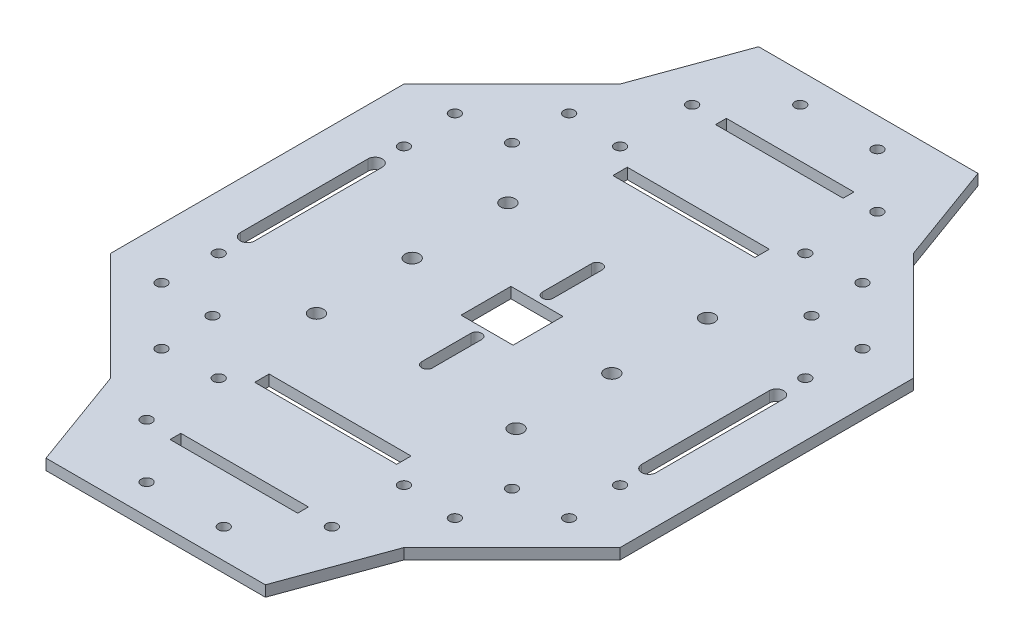
SolidWorks part; units mm, degrees
ref_plane "前视基准面" through (0, 0, 0) normal (0, 0, 1) x (1, 0, 0)
ref_plane "上视基准面" through (0, 0, 0) normal (0, 1, 0) x (1, 0, 0)
ref_plane "右视基准面" through (0, 0, 0) normal (1, 0, 0) x (0, 0, -1)
other "Configuration Table"
sketch "草图1" plane through (0, 0, 0) normal (0, 1, 0) x (1, 0, 0)
  line L0 (-70.7107, -70.7107) -> (70.7107, -70.7107)
  line L3 (70.7107, -70.7107) -> (70.7107, 70.7107)
  line L4 (70.7107, 70.7107) -> (-70.7107, 70.7107)
  line L5 (-70.7107, 70.7107) -> (-70.7107, -70.7107)
extrude "凸台-拉伸1" add sketch "草图1" along normal blind 3
sketch "草图2" plane through (0, 0, 0) normal (0, 1, 0) x (1, 0, 0)
  line L0 (-70.7107, 70.7107) -> (-40.7107, 70.7107)
  line L1 (70.7107, 70.7107) -> (-70.7107, 70.7107) construction
  line L2 (-70.7107, 70.7107) -> (-70.7107, 40.7107)
  line L3 (-70.7107, 70.7107) -> (-70.7107, -70.7107) construction
  line L4 (-40.7107, 70.7107) -> (-70.7107, 40.7107)
extrude "切除-拉伸1" cut sketch "草图2" along normal blind 3
mirror "镜向1" about plane through (0, 0, 0) normal (1, 0, 0) of "切除-拉伸1" second plane through (0, 0, 0) second plane normal (0, 0, 1)
sketch "草图3" plane through (0, 0, 0) normal (0, 1, 0) x (1, 0, 0)
  circle A0 centre (-56.5685, 40.7107) radius 1.5
  circle A1 centre (-40.7107, 56.5685) radius 1.5
  circle A2 centre (-41.5685, 41.5685) radius 1.5
extrude "切除-拉伸2" cut sketch "草图3" along normal blind 3
mirror "镜向2" about plane through (0, 0, 0) normal (0, 0, 1) of "切除-拉伸2" second plane through (0, 0, 0) second plane normal (1, 0, 0)
sketch "草图4" plane through (0, 0, 0) normal (0, 1, 0) x (1, 0, 0)
  circle A0 centre (-27.7107, 26.5685) radius 2
  circle A1 centre (-27.7107, -26.5685) radius 2
  circle A2 centre (-27.7107, 0) radius 2
extrude "切除-拉伸3" cut sketch "草图4" along normal blind 3
mirror "镜向3" about plane through (0, 0, 0) normal (1, 0, 0) of "切除-拉伸3"
sketch "草图5" plane through (0, 0, 0) normal (0, 1, 0) x (1, 0, 0)
  circle A0 centre (-55.7107, 25.7107) radius 1.5
extrude "切除-拉伸4" cut sketch "草图5" along normal blind 3
mirror "镜向4" about plane through (0, 0, 0) normal (1, 0, 0) of "切除-拉伸4" second plane through (0, 0, 0) second plane normal (0, 0, 1)
sketch "草图6" plane through (0, 0, 0) normal (0, 1, 0) x (1, 0, 0)
  circle A0 centre (-25.7107, 55.7107) radius 1.5
extrude "切除-拉伸5" cut sketch "草图6" along normal blind 3
mirror "镜向5" about plane through (0, 0, 0) normal (0, 0, 1) of "切除-拉伸5" second plane through (0, 0, 0) second plane normal (1, 0, 0)
sketch "草图7" plane through (0, 0, 0) normal (0, 1, 0) x (1, 0, 0)
  line L3 (-55.7107, 17.7107) -> (-55.7107, -17.7107) construction
  line L4 (-53.7107, 17.7107) -> (-53.7107, -17.7107)
  line L5 (-57.7107, 17.7107) -> (-57.7107, -17.7107)
  arc A0 (-53.7107, 17.7107) -> (-57.7107, 17.7107) centre (-55.7107, 17.7107) ccw
  arc A1 (-57.7107, -17.7107) -> (-53.7107, -17.7107) centre (-55.7107, -17.7107) ccw
  point P4 (-55.7107, 0)
extrude "切除-拉伸6" cut sketch "草图7" along normal blind 3
mirror "镜向6" about plane through (0, 0, 0) normal (1, 0, 0) of "切除-拉伸6"
sketch "草图8" plane through (0, 0, 0) normal (0, 1, 0) x (1, 0, 0)
  line L3 (7.2183, 6.9207) -> (-7.2183, 6.9207)
  line L4 (-7.2183, 6.9207) -> (-7.2183, -6.9207)
  line L5 (-7.2183, -6.9207) -> (7.2183, -6.9207)
  line L6 (7.2183, -6.9207) -> (7.2183, 6.9207)
extrude "切除-拉伸7" cut sketch "草图8" along normal blind 3
sketch "草图9" plane through (0, 0, 0) normal (0, 1, 0) x (1, 0, 0)
  line L5 (0, -9.9207) -> (0, -23.5685) construction
  line L6 (1.5, -9.9207) -> (1.5, -23.5685)
  line L7 (-1.5, -9.9207) -> (-1.5, -23.5685)
  arc A0 (1.5, -9.9207) -> (-1.5, -9.9207) centre (0, -9.9207) ccw
  arc A1 (-1.5, -23.5685) -> (1.5, -23.5685) centre (0, -23.5685) ccw
  point P10 (0, -16.7446)
extrude "切除-拉伸8" cut sketch "草图9" along normal blind 3
mirror "镜向7" about plane through (0, 0, 0) normal (0, 0, 1) of "切除-拉伸8"
sketch "草图10" plane through (0, 0, 0) normal (0, 1, 0) x (1, 0, 0)
  line L0 (-19.7107, 51.7107) -> (-19.7107, 51.4904)
  line L4 (-19.7107, 51.7107) -> (19.7107, 51.7107)
  line L5 (19.7107, 51.7107) -> (19.7107, 47.7107)
  line L6 (19.7107, 47.7107) -> (-19.7107, 47.7107)
  line L7 (-19.7107, 47.7107) -> (-19.7107, 51.4904)
extrude "切除-拉伸10" cut sketch "草图10" along normal blind 3
mirror "镜向8" about plane through (0, 0, 0) normal (0, 0, 1) of "切除-拉伸10"
sketch "草图11" plane through (0, 3, 0) normal (0, 1, 0) x (1, 0, 0)
  line L0 (-40.7107, 70.7107) -> (-30.4501, 98.9015)
  line L1 (40.7107, 70.7107) -> (30.4501, 98.9015)
  line L3 (-30.4501, 98.9015) -> (30.4501, 98.9015)
  line L4 (-40.7107, 70.7107) -> (40.7107, 70.7107)
extrude "凸台-拉伸2" add sketch "草图11" against normal blind 3
mirror "镜向9" about plane through (0, 0, 0) normal (1, 0, 0) of "凸台-拉伸2" second plane through (0, 0, 0) second plane normal (0, 0, 1)
sketch "草图13" plane through (0, 0, 0) normal (0, -1, 0) x (1, 0, 0)
  line L6 (-17.7107, 75.7107) -> (-17.7107, 77.2107)
  line L7 (-17.7107, 75.7107) -> (-17.7107, 74.2107)
  line L8 (-17.7107, 74.2107) -> (0, 74.2107)
  line L9 (0, 74.2107) -> (0, 77.2107)
  line L10 (0, 77.2107) -> (-17.7107, 77.2107)
  circle A0 centre (-25.7107, 75.7107) radius 1.5
  circle A1 centre (-10.7107, 90.7107) radius 1.5
extrude "切除-拉伸11" cut sketch "草图13" against normal blind 3
mirror "镜向10" about plane through (0, 0, 0) normal (1, 0, 0) of "切除-拉伸11"
mirror "镜向11" about plane through (0, 0, 0) normal (0, 0, 1) of "镜向10"
